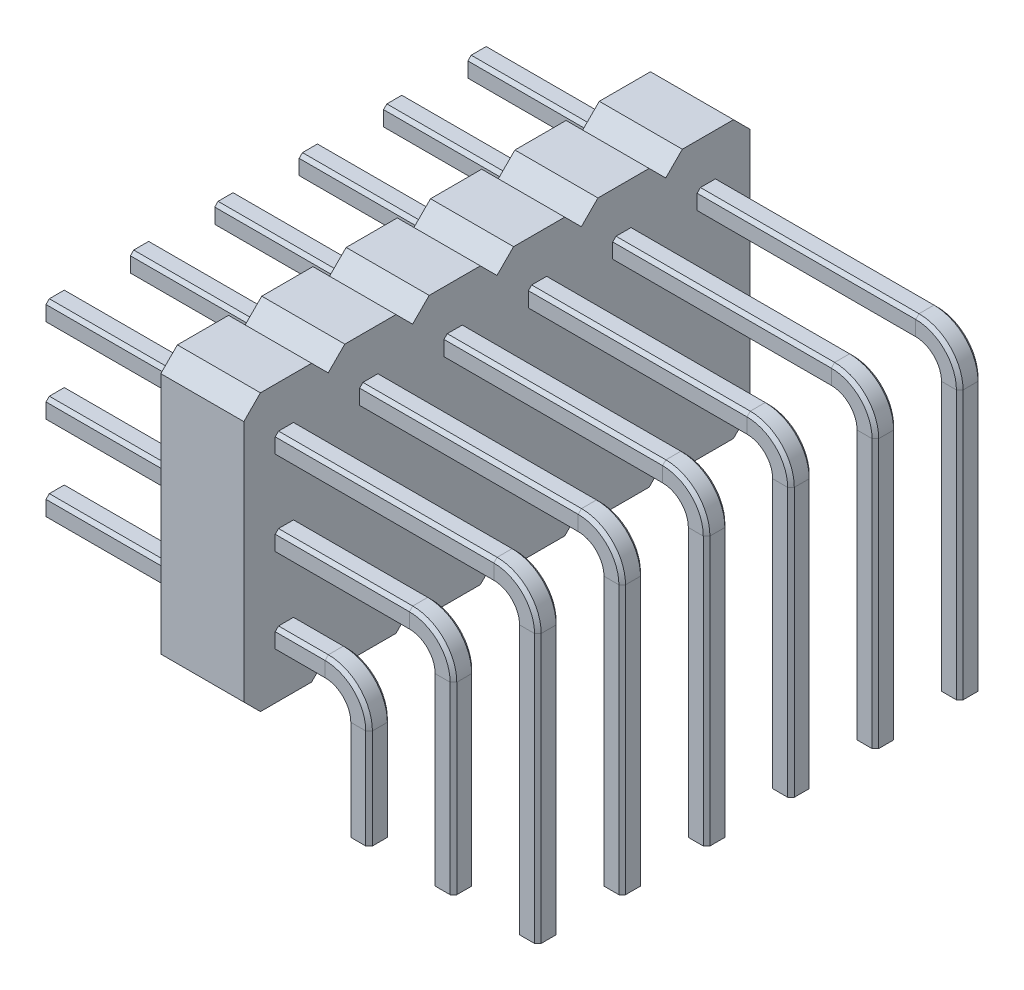
SolidWorks part; units mm, degrees
ref_plane "Front Plane" through (0, 0, 0) normal (0, 0, 1) x (1, 0, 0)
ref_plane "Top Plane" through (0, 0, 0) normal (0, 1, 0) x (1, 0, 0)
ref_plane "Right Plane" through (0, 0, 0) normal (1, 0, 0) x (0, 0, -1)
sketch "Sketch1" plane through (0, 0, 0) normal (0, 1, 0) x (1, 0, 0)
  line L0 (-0.225, 0.325) -> (-0.325, 0.225)
  line L1 (0.225, -0.325) -> (-0.225, -0.325)
  line L2 (0.325, -0.225) -> (0.325, 0.225)
  line L3 (0.225, 0.325) -> (-0.225, 0.325)
  line L4 (-0.325, -0.225) -> (-0.325, 0.225)
  line L5 (0.325, -0.325) -> (-0.325, 0.325) construction
  line L6 (0.325, 0.325) -> (-0.325, -0.325) construction
  line L7 (0.325, 0.225) -> (0.225, 0.325)
  line L8 (0.325, -0.225) -> (0.225, -0.325)
  line L9 (-0.225, -0.325) -> (-0.325, -0.225)
  line L10 (2.765, 0.325) -> (2.315, 0.325)
  line L11 (2.865, 0.225) -> (2.765, 0.325)
  line L12 (2.865, -0.225) -> (2.865, 0.225)
  line L13 (2.865, -0.225) -> (2.765, -0.325)
  line L14 (2.765, -0.325) -> (2.315, -0.325)
  line L15 (2.315, -0.325) -> (2.215, -0.225)
  line L16 (2.215, -0.225) -> (2.215, 0.225)
  line L17 (2.315, 0.325) -> (2.215, 0.225)
  line L18 (5.305, 0.325) -> (4.855, 0.325)
  line L19 (5.405, 0.225) -> (5.305, 0.325)
  line L20 (5.405, -0.225) -> (5.405, 0.225)
  line L21 (5.405, -0.225) -> (5.305, -0.325)
  line L22 (5.305, -0.325) -> (4.855, -0.325)
  line L23 (4.855, -0.325) -> (4.755, -0.225)
  line L24 (4.755, -0.225) -> (4.755, 0.225)
  line L25 (4.855, 0.325) -> (4.755, 0.225)
  point P0 (0, 0)
  dimension "D1" = 0.65
  dimension "D2" = 3
sketch "Sketch5" plane through (0, 0, 0) normal (0, 0, 1) x (1, 0, 0)
  line L0 (5.08, 0) -> (5.08, 8.08)
  line L1 (5.305, 0) -> (4.855, 0) construction
  line L2 (4.08, 9.08) -> (-9.4, 9.08)
  line L3 (2.54, 0) -> (2.54, 5.54)
  line L4 (2.765, 0) -> (2.315, 0) construction
  line L5 (1.54, 6.54) -> (-9.4, 6.54)
  line L6 (0, 0) -> (0, 3)
  line L7 (-1, 4) -> (-9.4, 4)
  arc A0 (0, 3) -> (-1, 4) centre (-1, 3) ccw
  arc A1 (2.54, 5.54) -> (1.54, 6.54) centre (1.54, 5.54) ccw
  arc A2 (5.08, 8.08) -> (4.08, 9.08) centre (4.08, 8.08) ccw
  point P18 (0, 4)
  point P21 (2.54, 6.54)
  point P24 (5.08, 9.08)
  dimension "D5" = 1
  dimension "D1" = 9.08
  dimension "D2" = 14.48
  dimension "D3" = 6.54
  dimension "D4" = 4
sweep "Sweep3" add profiles "Sketch1" path "Sketch5"
sweep "Sweep4" add profiles "Sketch1<4>" path "Sketch5<4>"
sketch "Sketch1<4>" plane through (0, 0, 0) normal (0, 1, 0) x (1, 0, 0) same geometry as "Sketch1"
sketch "Sketch5<4>" plane through (0, 0, 0) normal (0, 0, 1) x (1, 0, 0) same geometry as "Sketch5"
sweep "Sweep5" add profiles "Sketch1<5>" path "Sketch5<5>"
sketch "Sketch1<5>" plane through (0, 0, 0) normal (0, 1, 0) x (1, 0, 0) same geometry as "Sketch1"
sketch "Sketch5<5>" plane through (0, 0, 0) normal (0, 0, 1) x (1, 0, 0) same geometry as "Sketch5"
ref_plane "Plane1" through (-2.5, 0, 0) normal (1, 0, 0) x (0, 0, -1)
sketch "Sketch6" plane through (-2.5, 0, 0) normal (1, 0, 0) x (0, 0, -1)
  line L0 (0, 9.823) -> (0, 3.2159) construction
  line L1 (0.225, 9.405) -> (-0.225, 9.405) construction
  line L2 (0.77, 2.3639) -> (-0.77, 2.3639)
  line L3 (1.27, 2.8639) -> (1.27, 10.175)
  line L4 (0.77, 10.675) -> (-0.77, 10.675)
  line L5 (-1.27, 2.8639) -> (-1.27, 10.175)
  line L6 (1.27, 2.3639) -> (-1.27, 10.675) construction
  line L7 (1.27, 10.675) -> (-1.27, 2.3639) construction
  line L8 (-0.77, 10.675) -> (-1.27, 10.175)
  line L9 (1.27, 10.175) -> (0.77, 10.675)
  line L10 (1.27, 2.8639) -> (0.77, 2.3639)
  line L11 (-0.77, 2.3639) -> (-1.27, 2.8639)
  point P3 (0, 6.5195)
  dimension "D1" = 1.27
  dimension "D2" = 2.54
extrude "Boss-Extrude1" add sketch "Sketch6" against normal blind 2.5
pattern_linear "LPattern1" count 6 spacing 2.54 along (0, 0, 1) of "Boss-Extrude1"
combine bodies "Combine1" operation type add bodies to combine 107 108 109 110 111 112
